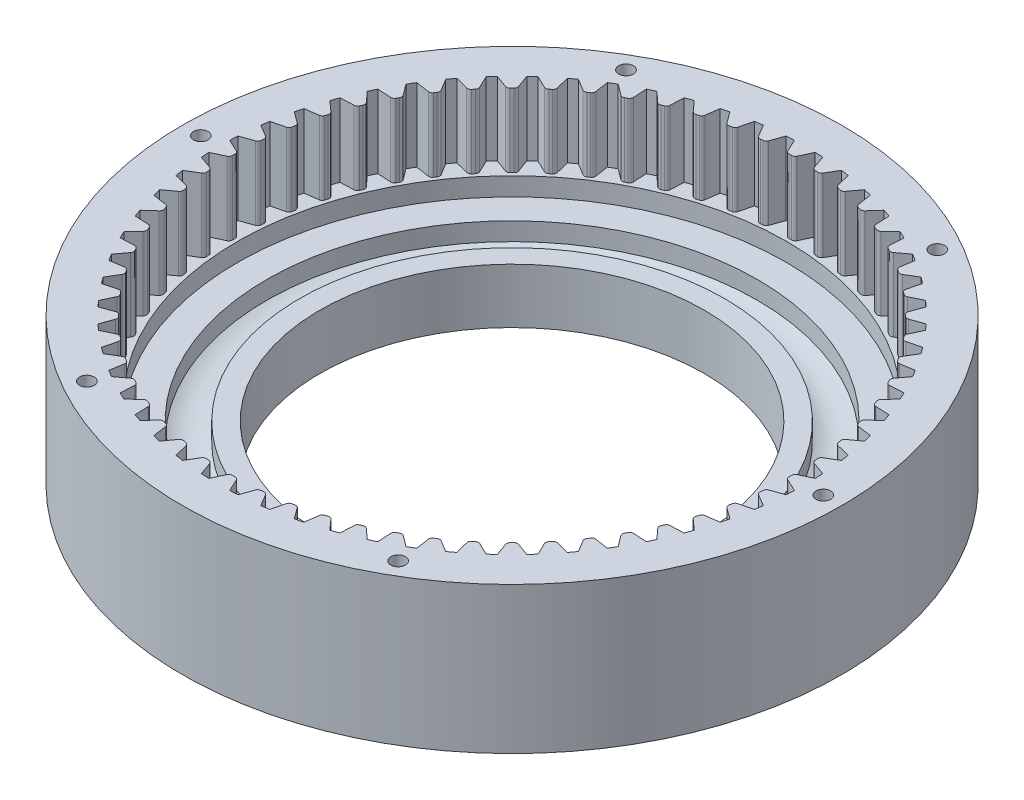
SolidWorks part; units mm, degrees
ref_plane "Front Plane" through (0, 0, 0) normal (0, 0, 1) x (1, 0, 0)
ref_plane "Top Plane" through (0, 0, 0) normal (0, 1, 0) x (1, 0, 0)
ref_plane "Right Plane" through (0, 0, 0) normal (1, 0, 0) x (0, 0, -1)
sketch "Sketch1" plane through (0, 0, 0) normal (0, 0, 1) x (1, 0, 0)
  line L0 (0, 0) -> (0, 36.773) construction
  line L1 (-52.5, 0) -> (-72.5, 0)
  line L2 (-90, 0) -> (-90, 40)
  line L3 (-90, 40) -> (-80, 40)
  line L4 (-80, 40) -> (-80, 20)
  line L5 (-75, 15) -> (-67, 15)
  line L6 (-67, 15) -> (-67, 10.0697)
  line L7 (-58, 10.0697) -> (-58, 15)
  line L8 (-58, 15) -> (-52.5, 15)
  line L10 (-67, 15) -> (-58, 15) construction
  line L12 (-52.5, 15) -> (-52.5, 0)
  line L13 (-82.5, 0) -> (-82.5, 5)
  line L14 (-82.5, 5) -> (-72.5, 5)
  line L15 (-72.5, 5) -> (-72.5, 0)
  line L16 (-82.5, 0) -> (-90, 0)
  line L18 (-80, 20) -> (-75, 20)
  line L19 (-75, 20) -> (-75, 15)
  arc A0 (-67, 10.0697) -> (-58, 10.0697) centre (-62.5, 19) ccw
  point P14 (-62.5, 15)
  point P16 (-62.5, 9)
  point P20 (-62.5, 0)
  dimension "D5" = 10
  dimension "D2" = 150
  dimension "D3" = 40
  dimension "D4" = 9
  dimension "D6" = 6
  dimension "D7" = 160
  dimension "D8" = 15
  dimension "D9" = 5
  dimension "D10" = 20
  dimension "D11" = 7.5
  dimension "D12" = 20
  dimension "D13" = 180
  dimension "D14" = 125
revolve "Revolve1" add sketch "Sketch1" angle 360 about L0
sketch "Sketch2" plane through (0, 20, 0) normal (0, 1, 0) x (1, 0, 0)
  line L0 (-79.9495, 2.8417) -> (-76.5774, 1.2692)
  line L1 (-76.5774, -1.2692) -> (-79.9495, -2.8417)
  line L2 (-76, -0.3629) -> (-76, 0.3629)
  circle A1 centre (0, 0) radius 80 construction
  circle A2 centre (0, 0) radius 80 construction
  arc A4 (-79.9495, 2.8417) -> (-79.9495, -2.8417) centre (0, 0) ccw
  arc A5 (-76, -0.3629) -> (-76.5774, -1.2692) centre (-77, -0.3629) cw
  arc A6 (-76.5774, 1.2692) -> (-76, 0.3629) centre (-77, 0.3629) cw
  point P9 (-76, -1)
  point P11 (-80, 0)
  point P15 (-76, 1)
  dimension "D1" = 4
  dimension "D4" = 1
  dimension "D2" = 50
  dimension "D3" = 2
extrude "Boss-Extrude1" add sketch "Sketch2" along normal up to surface (20 mm away) up to face at (0, 40, -90)
pattern_circular "CirPattern1" count 64 over 360 about axis through (0, 0, 0) along (0, -1, 0) of "Boss-Extrude1" reverse direction yes
sketch "Sketch3" plane through (0, 40, 0) normal (0, 1, 0) x (1, 0, 0)
  circle A0 centre (-85, 0) radius 2
  dimension "D2" = 4
  dimension "D1" = 85
extrude "Cut-Extrude1" cut sketch "Sketch3" against normal blind 15
pattern_circular "CirPattern2" count 6 over 360 about axis through (0, 0, 0) along (0, -1, 0) of "Cut-Extrude1" reverse direction yes
